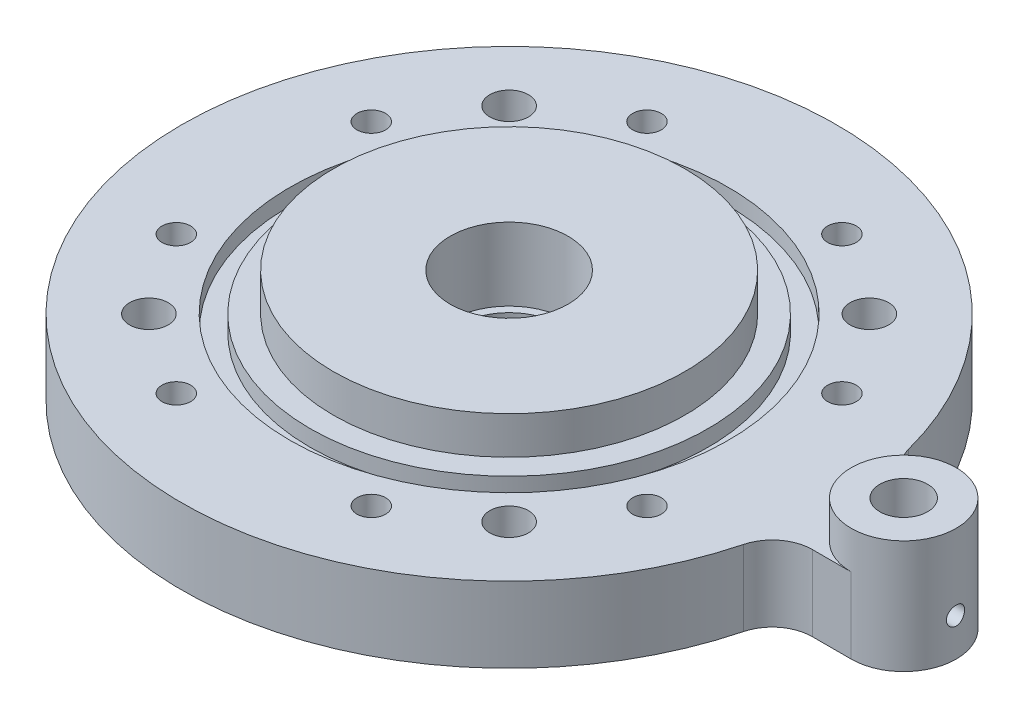
SolidWorks part; units mm, degrees
material "1060 Alloy"
ref_plane "Front" through (0, 0, 0) normal (0, 0, 1) x (1, 0, 0)
ref_plane "Top" through (0, 0, 0) normal (0, 1, 0) x (1, 0, 0)
ref_plane "Right" through (0, 0, 0) normal (1, 0, 0) x (0, 0, -1)
sketch "Sketch1" plane through (0, 0, 0) normal (0, 1, 0) x (1, 0, 0)
  line L0 (59.69, 0) -> (68.8572, 0) construction
  line L1 (62.0793, 9.1672) -> (68.8572, 9.1672)
  line L2 (62.0793, -9.1672) -> (68.8572, -9.1672)
  line L3 (59.69, 0) -> (78.0244, 0) construction
  line L4 (59.69, 0) -> (57.15, 0) construction
  arc A0 (55.3053, 14.403) -> (55.3053, -14.403) centre (0, 0) ccw
  circle A1 centre (0, 0) radius 57.15 construction
  arc A2 (68.8572, -9.1672) -> (68.8572, 9.1672) centre (68.8572, 0) ccw
  arc A3 (55.3053, 14.403) -> (62.0793, 9.1672) centre (62.0793, 16.1672) ccw
  arc A4 (62.0793, -9.1672) -> (55.3053, -14.403) centre (62.0793, -16.1672) ccw
  point P5 (34.5422, 0)
  point P10 (56.41, 9.1672)
  dimension "D1" = 114.3
  dimension "D4" = 7
  dimension "D2" = 18.3344
  dimension "D3" = 18.3344
  dimension "D5" = 2.54
extrude "base" add sketch "Sketch1" along normal blind 13.175
sketch "Sketch2" plane through (0, 13.175, 0) normal (0, 1, 0) x (1, 0, 0)
  line L0 (68.8572, 9.1672) -> (68.8572, -9.1672) construction
  circle A0 centre (0, 0) radius 30.6705
  arc A1 (68.8572, -9.1672) -> (68.8572, 9.1672) centre (68.8572, 0) ccw construction
  circle A2 centre (68.8572, 0) radius 9.1672
  circle A3 centre (68.8572, 0) radius 4.1672
  dimension "D1" = 61.341
  dimension "D2" = 8.3344
sketch "Sketch3" plane through (0, 0, 0) normal (0, -1, 0) x (1, 0, 0)
  line L0 (0, 0) -> (78.0244, 0) construction
  line L1 (0, 0) -> (40.4112, -40.4112) construction
  circle A0 centre (0, 0) radius 44.45 construction
  circle A1 centre (-31.4309, -31.4309) radius 3.3734
  circle A2 centre (-31.4309, 31.4309) radius 3.3734
  circle A3 centre (31.4309, 31.4309) radius 3.3734
  circle A4 centre (31.4309, -31.4309) radius 3.3734
  arc A5 (68.8572, -9.1672) -> (68.8572, 9.1672) centre (68.8572, 0) ccw construction
  arc A6 (55.3053, 14.403) -> (55.3053, -14.403) centre (0, 0) ccw construction
  point P14 (0, 0)
  dimension "D1" = 88.9
  dimension "D2" = 6.7469
  dimension "D4" = 45
  dimension "D3" = 4
extrude "square bolt holes" cut sketch "Sketch3" against normal through all
sketch "Sketch4" plane through (0, 13.175, 0) normal (0, 1, 0) x (1, 0, 0)
  line L0 (0, 0) -> (0, 44.45) construction
  line L1 (0, 44.45) -> (0, 0) construction
  line L2 (0, 0) -> (17.0103, 41.0664) construction
  circle A0 centre (0, 0) radius 44.45 construction
  circle A1 centre (17.0103, 41.0664) radius 2.5
  dimension "D1" = 88.9
  dimension "D3" = 5
  dimension "D2" = 22.5
extrude "housing bolts" cut sketch "Sketch4" against normal blind 44.33
pattern_circular "CirPattern1" count 8 over 360 about axis through (0, 13.175, 0) along (0, 1, 0) of "housing bolts"
extrude "impeller cavity riser" add sketch "Sketch2" along normal blind 6.59
sketch "Sketch5" plane through (0, 19.765, 0) normal (0, 1, 0) x (1, 0, 0)
  circle A0 centre (0, 0) radius 10.287
  dimension "D1" = 20.574
extrude "seal bore" cut sketch "Sketch5" against normal blind 12.7
sketch "Sketch6" plane through (0, 7.065, 0) normal (0, 1, 0) x (1, 0, 0)
  circle A0 centre (0, 0) radius 8.89
  dimension "D1" = 17.78
extrude "bore" cut sketch "Sketch6" against normal blind 39.3
sketch "pressure tap plane alignment" plane through (0, 0, 0) normal (0, -1, 0) x (1, 0, 0)
  line L1 (0, 0) -> (57.15, 0) construction
  line L2 (57.15, 0) -> (57.15, 57.15) construction
  line L3 (57.15, 57.15) -> (0, 57.15) construction
  circle A0 centre (0, 0) radius 57.15 construction
  circle A1 centre (0, 0) radius 57.15 construction
ref_plane "pressure tap plane" through (57.15, 0, 0) normal (1, 0, 0) x (0, 0, -1)
sketch "Sketch9" plane through (57.15, 0, 0) normal (1, 0, 0) x (0, 0, -1)
  line L0 (0, 0) -> (0, 13.175) construction
  line L1 (57.15, 13.175) -> (-57.15, 13.175) construction
  circle A0 centre (0, 6.5875) radius 1.5875
  dimension "D1" = 3.175
extrude "pressure tap" cut sketch "Sketch9" against normal blind 57.15 and the other way through all
sketch "Sketch10" plane through (0, 13.175, 0) normal (0, 1, 0) x (1, 0, 0)
  circle A0 centre (68.8572, 0) radius 1.5875
  dimension "D1" = 3.175
extrude "pressure tap vertical hole" cut sketch "Sketch10" against normal blind 8.175
sketch "Sketch12" plane through (0, 13.175, 0) normal (0, 1, 0) x (1, 0, 0)
  circle A0 centre (0, 0) radius 34.7218
  circle A1 centre (0, 0) radius 38.2524
  dimension "D1" = 76.5048
  dimension "D2" = 69.4436
extrude "o ring feature" cut sketch "Sketch12" against normal blind 2.8245
equation "\"de\" = 0.43in\t\t\t'entrance eye diameter"
equation "\"d2\" = 2.1in \t\t\t'outer diameter of the impeller"
equation "\"d_exit\" = 0.18in \t\t'throat aka d1"
equation "\"theta\" = 12\t\t\t'angle of blades from inner to outer "
equation "\"impeller upper clearance\"= .5mm"
equation "\"impeller horizontal clearance\"= (\"d2\"*1.15 - \"d2\")/2 \t\t'clearance based on D2-D3 ratio for circular volute, ranges 1.15 to 1.2"
equation "\"impeller bottom clearance\"= .5mm"
equation "\"impeller base thickness\"= 2mm"
equation "\"impeller dowel diameter\" = 2mm"
equation "\"impeller bolt head diameter\" = \"m4 head bore diameter\""
equation "\"impeller bolt head depth\" = 4mm"
equation "\"impeller bolt stop depth\" = 3mm"
equation "\"impeller bolt bore\" = \"m4 clearance\""
equation "\"impeller shaft bore depth\" = 12mm"
equation "\"impeller shaft bore\" = 8mm"
equation "\"impeller boss depth\" = \"impeller shaft bore depth\"+\"impeller bolt stop depth\"+\"impeller bolt head depth\"-\"impeller base thickness\""
equation "\"impeller boss diameter\" = \"upper seal ID\""
equation "\"impeller dowel length\" = 2mm*2 + \"impeller shaft bore\""
equation "\"coupler motor shaft hole ID\"= 8mm"
equation "\"coupler OD\"= 17mm"
equation "\"coupler length\"= 25mm"
equation "\"motor OD\" = 64mm"
equation "\"motor shaft diameter\"= 8mm"
equation "\"motor shaft pride\"= 32mm"
equation "\"motor to bearing plate distance\" = \"motor shaft pride\" + 2mm +\"coupler length\"/2"
equation "\"square plate bolt bore\" = \"m8 clearance\""
equation "\"square plate bolt head diameter\" = 13.5mm"
equation "\"square plate bolt pattern diameter\"= 3.5in"
equation "\"motor mount center bore\"= \"coupler OD\"+ 4mm"
equation "\"motor mount post radius\"= ( 3 * \"square plate bolt bore\" ) / 2"
equation "\"motor mount m4 screw hole diameter\"= 4mm"
equation "\"motor mount m4 head diameter\"= 7.25mm"
equation "\"motor mount m4 head depth\"= 4mm"
equation "\"motor mount m4 pattern diamater\" = 30mm"
equation "\"motor mount plate thickness\"= 8mm + \"motor mount m4 head depth\""
equation "\"shaft coupler section diameter\" = 8mm"
equation "\"shaft coupler section length\" = \"motor to bearing plate distance\" - \"motor shaft pride\" - 2mm"
equation "\"shaft bearing section diameter\" = \"bearing ID\""
equation "\"shaft bearing section length\" = \"bearing plate stop depth\" + \"bearing depth\""
equation "\"shaft bearing stop diameter\" = \"bearing ID\" + 4mm"
equation "\"shaft bearing stop length\" = 3mm"
equation "\"impeller cavity center height\"= \"impeller bottom clearance\" + \"impeller upper clearance\" + \"impeller center height\""
equation "\"impeller cavity diameter\"= 2 * \"impeller horizontal clearance\" + \"d2\" \t\t\t\t\t\t\t\t\t'called D3 analytically"
equation "\"impeller cavity outer height\"= \"impeller bottom clearance\" + \"impeller upper clearance\" + \"impeller base thickness\" + \"b2\" \t\t'this is height at impeller diameter d2, not at d3"
equation "\"impeller housing thickness\"= \"impeller housing exit threaded diameter\" + 2*\"impeller housing outlet grip\""
equation "\"impeller housing diameter\" = 4.5in"
equation "\"impeller housing bolt count\" = 8"
equation "\"impeller housing bolt diameter\" = \"m6 clearance\""
equation "\"impeller housing bolt pattern diameter\" = 3.5in"
equation "\"impeller housing threaded inlet diameter\" = 0.71875in \t'this is the 23/32 drill size for 1/2 NPT fitting https://www.mcmaster.com/#50715k269/=176pljy"
equation "\"impeller housing threaded inlet depth\"= .6in"
equation "\"impeller housing exit threaded diameter\"= 0.515625in \t\t'this is the 33/64 drill size for 9/16-18 fitting, expecting swagelok SS-8FK0-1-6STH fitting"
equation "\"impeller housing exit threaded depth\"= 10mm"
equation "\"impeller housing diffuser conical angle\"=10"
equation "\"impeller housing diffuser tangent angle\"=5"
equation "\"impeller housing outlet grip\" = 5mm"
equation "\"D1@Sketch1\"=\"impeller housing diameter\""
equation "\"D1@base\" = \"upper seal plate thickness\""
equation "\"D1@Sketch2\"=\"impeller cavity diameter\""
equation "\"D1@Sketch3\"=\"square plate bolt pattern diameter\""
equation "\"D2@Sketch3\"=\"m8 tap\""
equation "\"D1\"= \"upper seal plate thickness\" - 2mm"
equation "\"D1@Sketch4\"=\"impeller housing bolt pattern diameter\""
equation "\"D2@Sketch4\"=360/\"impeller housing bolt count\"/2"
equation "\"D3@Sketch4\"=\"m6 tap\""
equation "\"D1@CirPattern1\"=\"impeller housing bolt count\""
equation "\"D1@impeller cavity riser\" = \"upper seal plate riser\""
equation "\"D1@seal bore\" = \"upper seal bore\""
equation "\"D1@Sketch6\"=.7"
equation "\"D1@Sketch9\" = \"upper seal plate pressure hole diameter\""
equation "\"D1@pressure tap\"=\"impeller housing diameter\"/2"
equation "\"de_length\" = 4mm\t\t'entrance eye consistent length"
equation "\"square plate bolt head depth\" = 8mm"
equation "\"shaft impeller section diameter\" = \"impeller shaft bore\""
equation "\"shaft impeller section length\" = \"upper seal plate thickness\" + \"upper seal plate riser\" + \"impeller bottom clearance\" + \"impeller base thickness\" - \"impeller bolt head depth\" - \"impeller bolt stop depth\""
equation "\"impeller housing diffuser final diameter\" = .38in\t\t'aka d2'"
equation "\"D2@Sketch1\" = \"upper seal plate pressure tap diameter\" + \"upper seal plate pressure tap grip\" * 2"
equation "\"D3@Sketch1\" = \"upper seal plate pressure tap diameter\" + \"upper seal plate pressure tap grip\" * 2"
equation "\"D2@pressure tap\"=\"big seal plate pressure tap diameter\"/2+\"big seal plate pressure tap grip\""
equation "\"D2@Sketch2\" = \"upper seal plate pressure tap diameter\""
equation "\"D1@Sketch10\" = \"upper seal plate pressure hole diameter\""
equation "\"D1@pressure tap vertical hole\"= \"upper seal plate thickness\" / 2 + \"upper seal plate pressure hole diameter\" / 2"
equation "\"end mill size\" = 0.375in\t'for 3/8 endmill"
equation "\"m6 clearance\" = 0.234375in\t'this is 15/64 bit = 5.95mm, could use 6mm bit, B bit for 6.04mm or 1/4 bit for 6.35mm"
equation "\"m6 tap\" = 5mm\t\t\t'5mm is appropriate, could use 13/64 or #5,6,7"
equation "\"m6 head bore diameter\" = 11mm\t\t"
equation "\"m6 head bore depth\" = 7mm\t'actual is 6mm"
equation "\"m8 clearance\" = 0.3125in\t'this is 5/16in for 7.93mm, could use 8mm, O,P, or 21/64"
equation "\"m8 tap\" = 0.265625in\t\t'this is 17/64 for 6.746875mm"
equation "\"m8 head bore diameter\" = 14mm"
equation "\"m8 head bore depth\" = 9mm\t'actual is 8mm"
equation "\"ce\" = 3.14*\"de\"\t\t'entrance eye circumference"
equation "\"s_open\" = \"av\"/\"b1\"\t\t'width of open area"
equation "\"impeller center height\" = \"impeller base thickness\" + \"b1\"\t'impeller height at de"
equation "\"impeller outer height\" = \"impeller base thickness\" + \"b2\"\t'impeller height at de"
equation "\"lower seal OD\" = .917in\t\t'this is https://www.mcmaster.com/#9281k121/=174001b"
equation "\"lower seal ID\"= .375in"
equation "\"lower seal depth\" = .625in + .218in"
equation "\"lower seal bore\" = \"lower seal depth\" + 1mm"
equation "\"upper seal OD\" = 1.125in\t'this is https://www.mcmaster.com/#5154t33/=173zuau, needs to be visually inspected before machining!"
equation "\"upper seal ID\"= 0.625in"
equation "\"upper seal depth\"= .25in\t'aka height; these values need to be confirmed by inspection!! We may want to compress the height."
equation "\"upper seal bore\" = \"upper seal depth\" + 1mm"
equation "\"lower seal plate lip depth\" = 2mm"
equation "\"lower seal plate lip ID\" = \"lower seal OD\" - 3mm"
equation "\"lower seal plate thickness\" = \"lower seal plate lip depth\" + \"lower seal bore\""
equation "\"shaft lower seal section diameter\" = \"lower seal ID\""
equation "\"shaft lower seal section length\" = \"lower seal plate thickness\" + 1mm"
equation "\"upper seal plate thickness\" = \"upper seal plate pressure hole diameter\"+10mm"
equation "\"upper seal plate lip ID\" = \"upper seal OD\" - 3mm"
equation "\"upper seal plate riser\" = 6.59mm \t\t'this number needs to be read from the housing file"
equation "\"upper seal plate pressure hole diameter\" = .125in\t'this is 1/8 drill "
equation "\"upper seal plate pressure tap diameter\" = .328125in \t'this is 21/64 drill for a 1/8 ANPT tap"
equation "\"upper seal plate pressure tap grip\" = 5mm\t\t'this is the area around the tap so it doesn't crack"
equation "\"upper seal plate pressure tap depth\" = 12mm"
equation "\"bearing OD\" = 30mm"
equation "\"bearing ID\"= 10mm"
equation "\"bearing depth\"= 9mm"
equation "\"bearing outer race thickness\"= 1mm"
equation "\"bearing inner race thickness\"= 1mm"
equation "\"bearing bore\" = \"bearing depth\" + 1mm"
equation "\"z\" = 8\t\t\t\t'number of blades"
equation "\"b2\" = .2in\t\t\t'tip height from disc surface at d2; slightly higher than d_exit"
equation "\"b1\" = \"b2\" + (\"d2\"/2 - \"de\"/2)*tan(\"theta\") \t\t\t'tip height from disc surface at inlet eye"
equation "\"ae\" = 3.14*(\"de\"^2)/4\t\t'entrance eye area'"
equation "\"av_ratio\" = .325\t\t'ratio of av/ae at N_s of 470, range is .275 to .375, .325 ideal. High ratio means bigger area means smaller blades"
equation "\"av\" = \"ae\"*\"av_ratio\"\t\t'area between just two blades"
equation "\"s\"=\"ce\" - \"z\"*\"s_open\""
equation "\"bearing plate stop ID\" = \"bearing OD\" - 4mm"
equation "\"bearing plate stop depth\" = 3mm"
equation "\"bearing plate thickness\" = \"bearing bore\" + \"bearing plate stop depth\" + \"shaft bearing stop length\""
equation "\"m4 clearance\" = 0.171875in \t'this is 11/64 bit for 4.36mm"
equation "\"m4 tap\" = 0.125in\t\t'this is 1/8 bit for 3.17mm"
equation "\"m4 head bore diameter\" = 7.5mm"
equation "\"m4 head bore depth\" = 5mm\t'actual is ~4mm"
equation "\"big o-ring thickness\" = .139in"
equation "\"big o-ring OD\" = 2.734in"
equation "\"big o-ring ID\" = 3.012in"
equation "\"big o-ring groove depth\" = \"big o-ring thickness\"*4/5"
equation "\"D1@Sketch12\"=\"big o-ring ID\""
equation "\"D2@Sketch12\"=\"big o-ring OD\""
equation "\"D1@o ring feature\" = \"big o-ring groove depth\""
equation "\"min blade thickness\" = .15in"
equation "\"diffuser cartridge OD\" =.75in"
equation "\"diffuser flange bolt pattern diameter\" = 1.4in"
